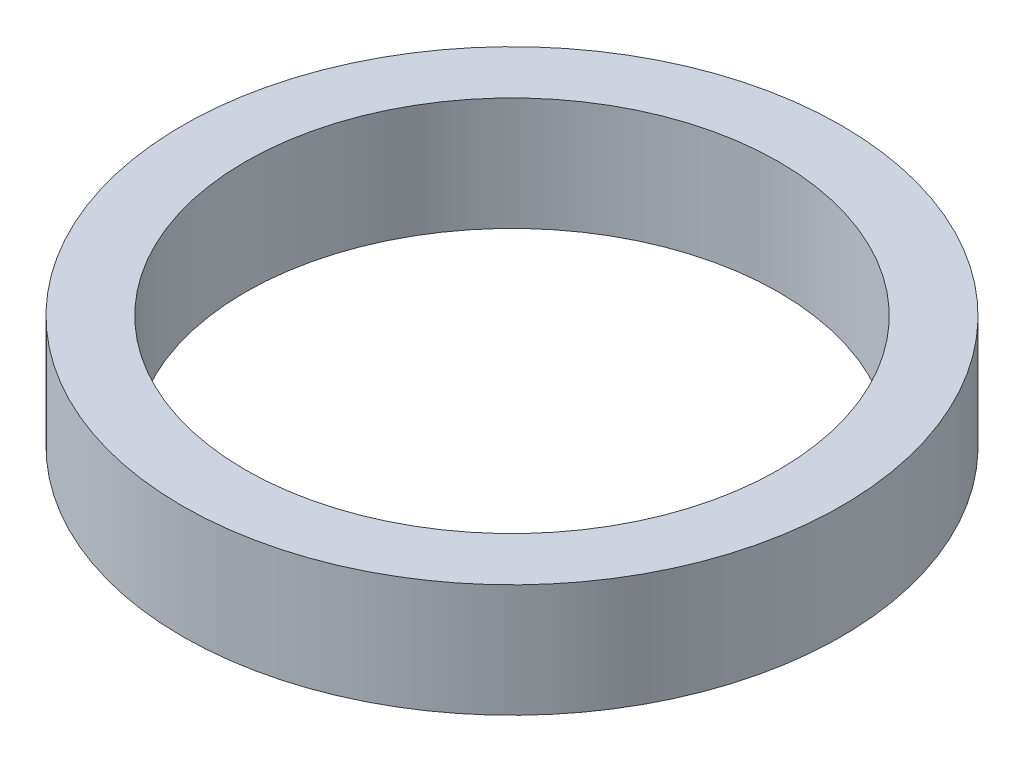
SolidWorks part; units mm, degrees
ref_plane "Front Plane" through (0, 0, 0) normal (0, 0, 1) x (1, 0, 0)
ref_plane "Top Plane" through (0, 0, 0) normal (0, 1, 0) x (1, 0, 0)
ref_plane "Right Plane" through (0, 0, 0) normal (1, 0, 0) x (0, 0, -1)
sketch "Sketch1" plane through (0, 0, 0) normal (0, 1, 0) x (1, 0, 0)
  circle A0 centre (0, 0) radius 52.5
  dimension "FLANGE_OD" = 105
extrude "Boss-Extrude1" add sketch "Sketch1" along normal blind 18
sketch "Sketch2" plane through (0, 0, 0) normal (0, 1, 0) x (1, 0, 0)
  circle A0 centre (0, 0) radius 42.5
  dimension "BORE_D" = 85
extrude "Cut-Extrude1" cut sketch "Sketch2" along normal through all
sketch "Sketch3" plane through (0, 18, 0) normal (0, 1, 0) x (1, 0, 0)
  circle A0 centre (0, 0) radius 22.8585 construction
  circle A1 centre (-22.8585, 0) radius 1.589
  dimension "BOLT_D" = 3.1781
  dimension "BOLT_PCD" = 45.7169
extrude "Cut-Extrude2" cut sketch "Sketch3" against normal blind 11.5796 rebuild error yes
pattern_circular "CirPattern1" count 8 over 360 rebuild error yes
